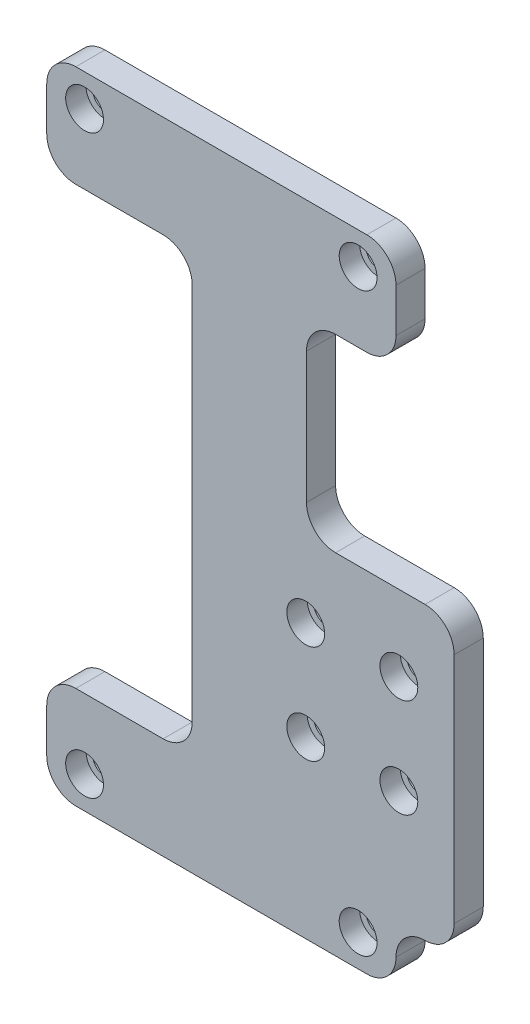
SolidWorks part; units mm, degrees
other "Markup1"
sketch "Sketch8" plane through (70, 0, 0) normal (0.012, -0.3966, -0.9179) x (-0.0069, -0.918, 0.3965)
ref_plane "Front Plane" through (0, 0, 0) normal (0, 0, 1) x (1, 0, 0)
ref_plane "Top Plane" through (0, 0, 0) normal (0, 1, 0) x (1, 0, 0)
ref_plane "Right Plane" through (0, 0, 0) normal (1, 0, 0) x (0, 0, -1)
sketch "Sketch1" plane through (0, 0, 0) normal (0, 0, 1) x (1, 0, 0)
  line L0 (60, 40) -> (60, 110)
  line L1 (0, 0) -> (60, 0)
  line L2 (0, 0) -> (0, 110)
  line L3 (0, 110) -> (60, 110)
  line L4 (60, 0) -> (60, 40)
  dimension "D1" = 110
  dimension "D2" = 60
extrude "Boss-Extrude1" add sketch "Sketch1" along normal blind 5
sketch "Sketch3" plane through (0, 0, 5) normal (0, 0, 1) x (1, 0, 0)
  line L0 (30, 0) -> (30, 9.5665) construction
  line L1 (0, 0) -> (60, 0) construction
  line L2 (0, 55) -> (10.8877, 55) construction
  line L3 (0, 110) -> (0, 0) construction
  circle A0 centre (6.5, 5.5) radius 2.1
  circle A1 centre (53.5, 5.5) radius 2.1
  circle A2 centre (53.5, 104.5) radius 2.1
  circle A3 centre (6.5, 104.5) radius 2.1
  dimension "D1" = 4.2
  dimension "D2" = 5.5
  dimension "D3" = 47
extrude "Cut-Extrude1" cut sketch "Sketch3" against normal blind 10
sketch "Sketch4" plane through (0, 0, 5) normal (0, 0, 1) x (1, 0, 0)
  line L0 (30, 0) -> (30, 110) construction
  line L1 (0, 0) -> (60, 0) construction
  line L2 (60, 110) -> (0, 110) construction
  line L3 (52.5, 47) -> (52.5, 30) construction
  line L6 (60, 0) -> (60, 110) construction
  line L7 (44.5, 30) -> (60.5, 30) construction
  line L8 (44.5, 47) -> (60.5, 47) construction
  line L9 (52.5, 38.5) -> (52.5, 76.5)
  line L11 (60, 60) -> (70, 60)
  line L12 (60, 60) -> (60, 10)
  line L13 (60, 10) -> (70, 10)
  line L14 (70, 60) -> (70, 10)
  circle A0 centre (60.5, 30) radius 2.1
  circle A1 centre (44.5, 30) radius 2.1
  circle A2 centre (44.5, 47) radius 2.1
  circle A3 centre (60.5, 47) radius 2.1
  point P13 (63.214, 47)
  point P15 (52.5, 30)
  point P18 (52.5, 47)
  line M13 (60, 0) -> (60, 110)
  dimension "D5" = 4.2
  dimension "D1" = 22.5
  dimension "D2" = 38
  dimension "D3" = 17
  dimension "D4" = 16
  dimension "D6" = 30
  dimension "D7" = 10
  dimension "D8" = 50
  dimension "D9" = 10
extrude "Boss-Extrude2" add sketch "Sketch4" against normal blind 5 contours L14 L11 L13 A3 A0 M13 region at (65.1447, 34.8692, 5)
extrude "Cut-Extrude2" cut sketch "Sketch4<3>" against normal blind 5 contours A1 | A2 | A3 | A0
sketch "Sketch4<3>" plane through (0, 0, 5) normal (0, 0, 1) x (1, 0, 0) same geometry as "Sketch4"
fillet "Fillet1" radius 5 2 edges at (0, 110, 2.5) (0, 0, 2.5)
sketch "Sketch5" plane through (0, 0, 5) normal (0, 0, 1) x (1, 0, 0)
  line L0 (0, 17.5) -> (25, 17.5)
  line L3 (25, 17.5) -> (25, 92.5)
  line L4 (25, 92.5) -> (0, 92.5)
  line L5 (0, 17.5) -> (0, 92.5)
  line L6 (0, 105) -> (0, 5) construction
  line L7 (60, 60) -> (44.628, 60)
  line L8 (44.628, 60) -> (44.628, 92.5)
  line L10 (44.628, 92.5) -> (60, 92.5)
  line L11 (60, 60) -> (60, 110) construction
  line L12 (60, 92.5) -> (60, 60)
  point P4 (0, 55)
  point P5 (0, 55)
  dimension "D1" = 25
  dimension "D2" = 75
extrude "Cut-Extrude3" cut sketch "Sketch5" against normal blind 5
fillet "Fillet2" radius 5 12 edges at (60, 0, 2.5) (60, 10, 2.5) (70, 10, 2.5) (70, 60, 2.5) (60, 92.5, 2.5) (60, 110, 2.5) (44.628, 92.5, 2.5) (44.628, 60, 2.5) (0, 17.5, 2.5) (25, 17.5, 2.5) (25, 92.5, 2.5) (0, 92.5, 2.5)
sketch "Sketch6" plane through (0, 0, 5) normal (0, 0, 1) x (1, 0, 0)
  circle A0 centre (44.5, 47) radius 3.25
  circle A1 centre (60.5, 47) radius 3.25
  circle A2 centre (60.5, 30) radius 3.25
  circle A3 centre (44.5, 30) radius 3.25
  circle A4 centre (53.5, 5.5) radius 3.25
  circle A5 centre (6.5, 5.5) radius 3.25
  circle A6 centre (6.5, 104.5) radius 3.25
  circle A7 centre (53.5, 104.5) radius 3.25
  dimension "D1" = 6.5
extrude "Cut-Extrude4" cut sketch "Sketch6" against normal blind 3.5
sketch "Sketch9" plane through (0, 0, 0) normal (0, 0, -1) x (-1, 0, 0)
  line L0 (-30, 110) -> (-30, 0) construction
  line L1 (-55, 110) -> (-5, 110) construction
  line L2 (-5, 0) -> (-55, 0) construction
  line L3 (-30, 55) -> (-49.9749, 55) construction
